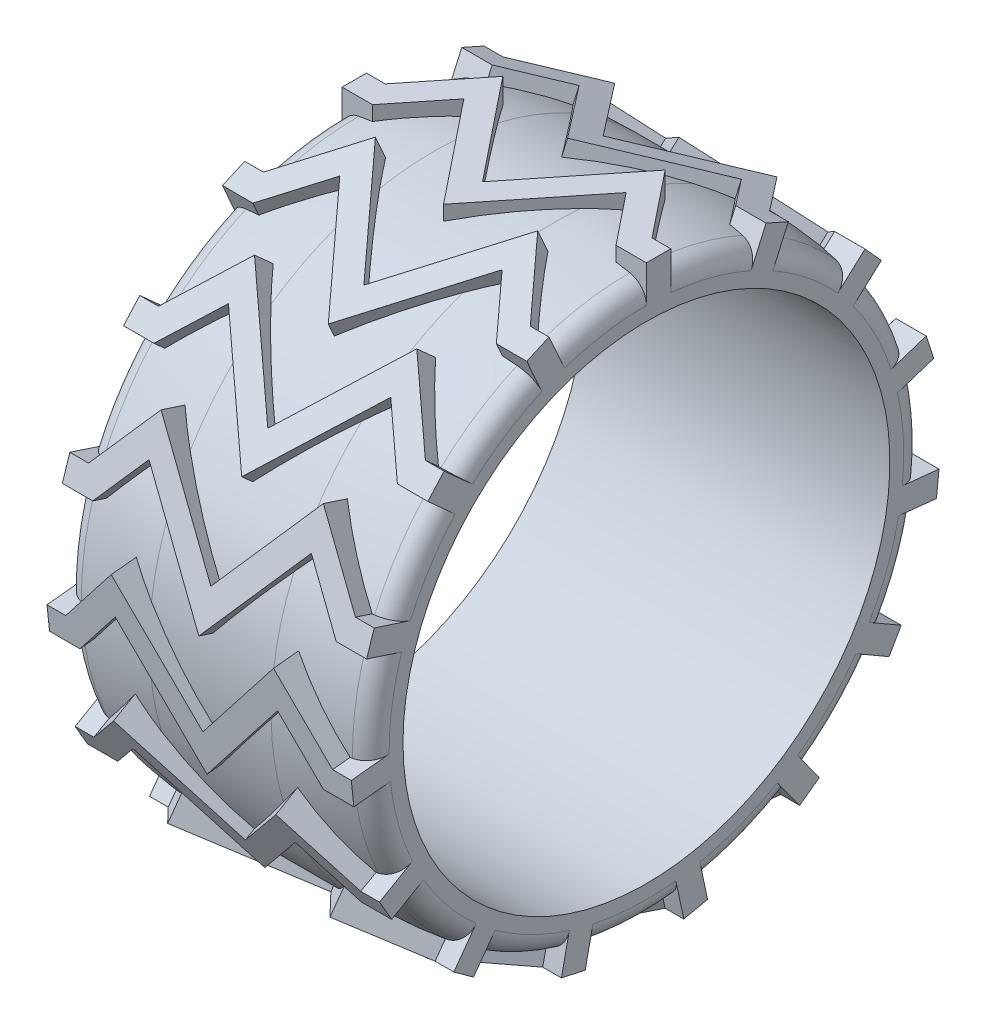
SolidWorks part; units mm, degrees
material "ABS"
ref_plane "Front Plane" through (0, 0, 0) normal (0, 0, 1) x (1, 0, 0)
ref_plane "Top Plane" through (0, 0, 0) normal (0, 1, 0) x (1, 0, 0)
ref_plane "Right Plane" through (0, 0, 0) normal (1, 0, 0) x (0, 0, -1)
sketch "Sketch1" plane through (0, 0, 0) normal (0, 0, 1) x (1, 0, 0)
  line L0 (0, 70.6667) -> (0, -99) construction
  line L1 (-30, 0) -> (30, 0)
  line L2 (-75, -20) -> (75, -20)
  line L3 (-160.0287, -140) -> (296.3361, -140) construction
  line L4 (-75, -20) -> (-75, -5)
  line L5 (75, -20) -> (75, -5)
  arc A0 (-75, -5) -> (-30, 0) centre (-30, -205) cw
  arc A1 (75, -5) -> (30, 0) centre (30, -205) ccw
  point P6 (0, 0)
  point P9 (0, -20)
  dimension "D1" = 20
  dimension "D2" = 30
  dimension "D3" = 75
  dimension "D4" = 205
  dimension "D5" = 15
  dimension "D6" = 205
  dimension "D7" = 280
revolve "Revolve1" add sketch "Sketch1" angle 360 about L3
sketch "Sketch2" plane through (0, 0, 0) normal (0, 1, 0) x (1, 0, 0)
  line L0 (-75, 0) -> (-60, 0)
  line L1 (-75, 135) -> (-75, -135) construction
  line L2 (-60, 0) -> (-40, 25)
  line L3 (-40, 25) -> (0, -25)
  line L4 (-40, 25) -> (-40, 0) construction
  line L5 (-40, 0) -> (0, 0) construction
  line L6 (0, 0) -> (0, -25) construction
  line L7 (40, 25) -> (0, -25)
  line L8 (60, 0) -> (40, 25)
  line L9 (75, 0) -> (60, 0)
  dimension "D1" = 15
  dimension "D2" = 35
  dimension "D3" = 25
extrude "Extrude-Thin1" add sketch "Sketch2" along normal blind 5 and the other way up to surface thin other way up to face at (75, -140, 120) thin type one direction wall 12
fillet "Fillet1" radius 10 2 edges at (75, -274.8663, 6.0059) (-75, -274.8663, 6.0059)
pattern_circular "CirPattern1" count 15 over 360 about axis through (75, -140, 0) along (-1, 0, 0) of "Extrude-Thin1"
